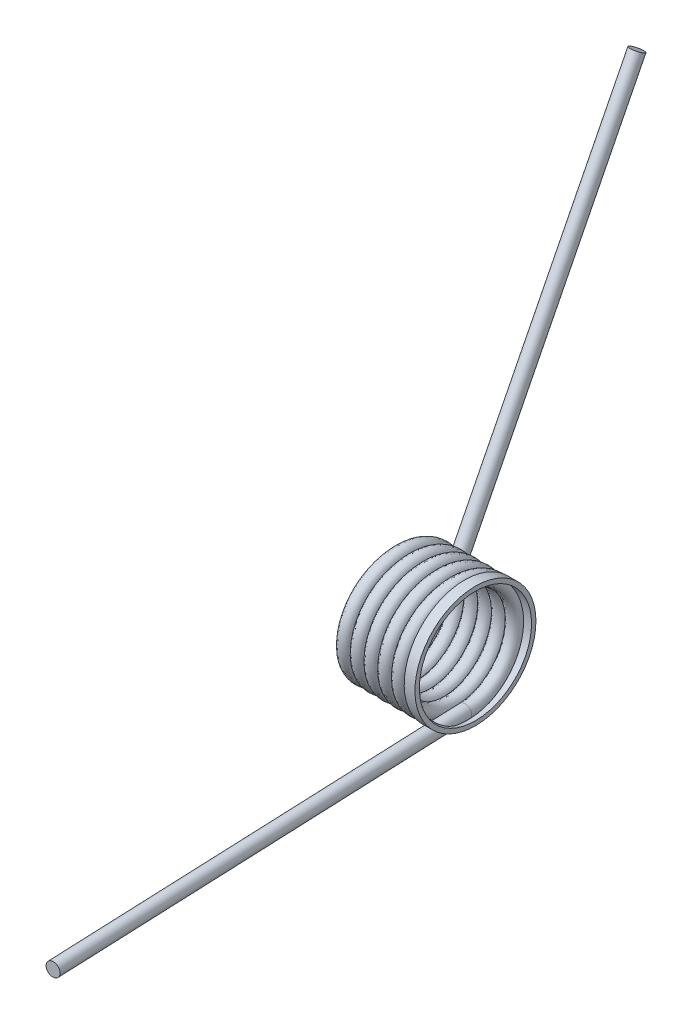
SolidWorks part; units mm, degrees
ref_plane "Front" through (0, 0, 0) normal (0, 0, 1) x (1, 0, 0)
ref_plane "Top" through (0, 0, 0) normal (0, 1, 0) x (1, 0, 0)
ref_plane "Right" through (0, 0, 0) normal (1, 0, 0) x (0, 0, -1)
sketch "Sketch1" plane through (0, 0, 0) normal (1, 0, 0) x (0, 0, -1)
  line L0 (0, -5.5118) -> (0, -7.112) construction
  line L1 (6.1592, -3.556) -> (31.5592, 40.4381) construction
  line L2 (0, -7.112) -> (-50.8, -7.112) construction
  line L3 (0, 0) -> (7.112, 0) construction
  line L4 (0, 0) -> (6.1592, -3.556) construction
  line L5 (-50.8, -7.112) -> (-50.8, -5.5118) construction
  line L6 (-50.8, -5.5118) -> (0, -5.5118) construction
  line L7 (31.5592, 40.4381) -> (30.1734, 41.2382) construction
  line L8 (30.1734, 41.2382) -> (4.7734, -2.7559) construction
  circle A0 centre (0, 0) radius 7.112 construction
  circle A1 centre (0, 0) radius 4.3561 construction
  circle A2 centre (0, 0) radius 6.3119 construction
  point P7 (0, -6.3119)
  point P10 (0, 7.112)
  dimension "OD" = 14.224
  dimension "For Shaft Diameter" = 8.7122
  dimension "Wire Diameter" = 1.6002
  dimension "Leg Length" = 50.8
  dimension "Deflection Angle" = 120
sketch "Sketch2" plane through (0, 0, 0) normal (1, 0, 0) x (0, 0, -1)
  circle A0 centre (0, 0) radius 6.3119 construction
  circle A2 centre (0, 0) radius 6.3119
curve "Helix/Spiral1" pitch 1.6256 height 8.3989 turns 5.1667
ref_plane "Plane1" through (0, -6.3119, 0) normal (-0.041, 0, -0.9992) x (0.9989, -0.0232, -0.0409)
sketch "Sketch3" plane through (0, -6.3119, 0) normal (-0.041, 0, -0.9992) x (0.9989, -0.0232, -0.0409)
  circle A0 centre (0, 0) radius 0.8001
  dimension "D1" = 1.6002
sweep "Sweep1" add profiles "Sketch3" path "Helix/Spiral1"
sketch "Sketch4" plane through (0, 0, 0) normal (0.041, 0, 0.9992) x (-0.9989, 0.0232, 0.0409)
  circle A1 centre (-0.1467, 6.3102) radius 0.8001
  circle A2 centre (-0.1467, 6.3102) radius 0.8001
  dimension "D1" = 0
extrude "Extrude1" add sketch "Sketch4" along normal blind 50.8
sketch "Sketch5" plane through (-0.0141, 0.2976, -0.1718) normal (-0.041, 0.8653, -0.4996) x (0.9992, 0.0355, -0.0204)
  circle A1 centre (-8.3921, 6.3116) radius 0.8001
  circle A2 centre (-8.3921, 6.3116) radius 0.8001
  dimension "D1" = 0
extrude "Extrude2" add sketch "Sketch5" along normal blind 50.8
sketch "Sketch6" plane through (0, 0, 0) normal (1, 0, 0) x (0, 0, -1)
  circle A2 centre (0, 0) radius 5.5118 construction
sketch "Sketch8" plane through (0, 0, 0) normal (1, 0, 0) x (0, 0, -1)
  circle A0 centre (0, 0) radius 7.1535
  circle A1 centre (0, 0) radius 6.6322
  circle A2 centre (0, 0) radius 5.5079 construction
  dimension "D1" = 11.0157
extrude "Boss-Extrude1" add sketch "Sketch8" along normal blind 1.27
equation "\"D4@Helix/Spiral1\" = \"Wire Diameter@Sketch1\" + .001"
equation "\"D1@Sketch3\"=\"Wire Diameter@Sketch1\""
equation "\"D1@Extrude2\"=\"Leg Length@Sketch1\""
equation "\"Leg Length@Extrude1\"=\"Leg Length@Sketch1\""
